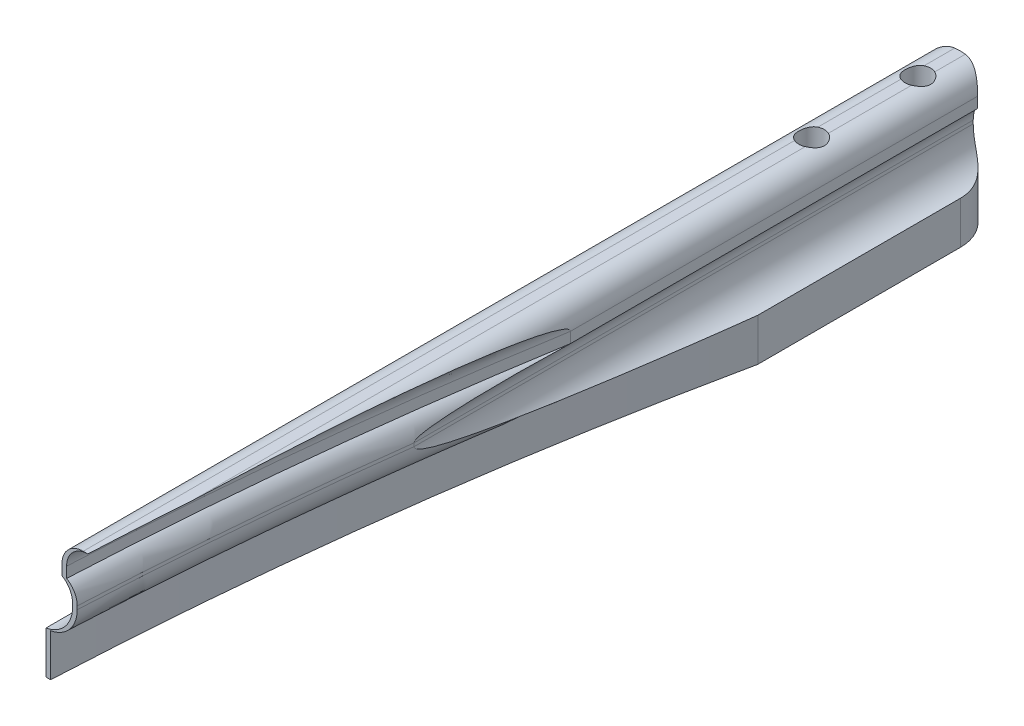
SolidWorks part; units mm, degrees
other "标注1"
sketch "草图3" plane through (-22.25, 4, -10) normal (-0.231, 0.6469, -0.7268) x (-0.9696, -0.2151, 0.1167)
other "标注2"
sketch "草图4" plane through (22.25, 8, -30) normal (0.0083, 0.0567, -0.9984) x (-0.9991, 0.0415, -0.0059)
ref_plane "前视基准面" through (0, 0, 0) normal (0, 0, 1) x (1, 0, 0)
ref_plane "上视基准面" through (0, 0, 0) normal (0, 1, 0) x (1, 0, 0)
ref_plane "右视基准面" through (0, 0, 0) normal (1, 0, 0) x (0, 0, -1)
other "Configuration Table"
sketch "草图1" plane through (0, 0, 0) normal (0, 1, 0) x (1, 0, 0)
  line L0 (-13.75, 12.5) -> (-13.75, -12.5)
  line L13 (-17.75, -12.5) -> (17.75, -12.5)
  line L21 (-17.75, -12.5) -> (-17.75, 12.5)
  line L22 (-17.75, 12.5) -> (17.75, 12.5)
  line L23 (17.75, -12.5) -> (17.75, 12.5)
  line L24 (-17.75, -12.5) -> (17.75, 12.5) construction
  line L25 (-17.75, 12.5) -> (17.75, -12.5) construction
  line L27 (13.75, 12.5) -> (13.75, -12.5)
  line L29 (-13.75, 0) -> (13.75, 0) construction
  line L32 (-22.25, 12.5) -> (22.25, 12.5)
  line L33 (-22.25, 12.5) -> (-22.25, 4.5)
  line L34 (-22.25, 4.5) -> (22.25, 4.5)
  line L35 (22.25, 12.5) -> (22.25, 4.5)
  point P0 (0, 0)
  point P15 (0, 4.5)
  dimension "D3" = 27.5
  dimension "D4" = 8
  dimension "D1" = 35.5
  dimension "D2" = 25
  dimension "D5" = 44.5
extrude "凸台-拉伸1" add sketch "草图1" along normal blind 4 contours L34 L21 L13 L0 | L34 L27 L13 L23 | L27 L34 L23 L22 | L21 L34 L0 L22 region at (-15.75, 0, -8.5) region at (-15.75, 0, 4) region at (15.75, 0, -8.5) region at (15.75, 0, 4)
extrude "凸台-拉伸2" add sketch "草图1<7>" along normal blind 3.5 contours L34 L35 L32 L33
sketch "草图1<7>" plane through (0, 0, 0) normal (0, 1, 0) x (1, 0, 0) same geometry as "草图1"
sketch "草图2" plane through (0, 0, -12.5) normal (0, 0, -1) x (-1, 0, 0)
  line L0 (18.25, 3.5) -> (22.25, 2)
  line L1 (22.25, 3.5) -> (18.25, 3.5)
  line L2 (22.25, 3.5) -> (22.25, 2)
  line L3 (22.25, 2) -> (18.25, 2) construction
  line L4 (18.25, 3.5) -> (18.25, 2) construction
  line L5 (-22.25, 2) -> (-18.25, 3.5)
  line L6 (-22.25, 3.5) -> (-18.25, 3.5)
  line L7 (-22.25, 3.5) -> (-22.25, 2)
  line L8 (-22.25, 2) -> (-18.25, 2) construction
  line L9 (-18.25, 3.5) -> (-18.25, 2) construction
  line L10 (13.75, 3.5) -> (-13.75, 3.5) construction
  line L11 (-13.25, 3.5) -> (-9.25, 3.5)
  line L12 (-13.25, 3.5) -> (-13.25, 2) construction
  line L13 (-13.25, 2) -> (-9.25, 2) construction
  line L14 (-9.25, 3.5) -> (-9.25, 2)
  line L15 (-13.75, 3.5) -> (-13.25, 3.5) construction
  line L16 (13.25, 3.5) -> (9.25, 3.5)
  line L17 (13.25, 3.5) -> (13.25, 2) construction
  line L18 (13.25, 2) -> (9.25, 2) construction
  line L19 (9.25, 3.5) -> (9.25, 2)
  line L20 (13.25, 3.5) -> (13.75, 3.5) construction
  line L21 (17.75, 3.5) -> (18.25, 3.5) construction
  line L22 (-13.25, 3.5) -> (-9.25, 2)
  line L23 (9.25, 2) -> (13.25, 3.5)
  line L24 (-9.25, 2) -> (9.25, 2)
  line L25 (-9.25, 3.5) -> (9.25, 3.5)
  line L26 (-15.75, 4) -> (-15.75, 6.5) construction
  line L27 (14.5, 8) -> (17, 8)
  line L28 (14.5, 8) -> (14.5, 6.5)
  line L29 (14.5, 6.5) -> (17, 6.5)
  line L30 (17, 8) -> (17, 6.5)
  line L31 (-17, 8) -> (-14.5, 8)
  line L32 (-17, 8) -> (-17, 6.5)
  line L33 (-17, 6.5) -> (-14.5, 6.5)
  line L34 (-14.5, 8) -> (-14.5, 6.5)
  line L35 (-13.75, 4) -> (-17.75, 4) construction
  line L36 (15.75, 6.5) -> (15.75, 4) construction
  line L37 (17.75, 4) -> (13.75, 4) construction
  line L38 (15, 6.5) -> (15, 4)
  line L39 (16.5, 6.5) -> (16.5, 4)
  line L40 (16.5, 4) -> (15.75, 4)
  line L41 (15.75, 4) -> (15, 4)
  line L42 (-16.5, 6.5) -> (-16.5, 4)
  line L43 (-16.5, 4) -> (-15.75, 4)
  line L44 (-15.75, 4) -> (-15, 4)
  line L45 (-15, 4) -> (-15, 6.5)
  line M9 (22.25, 3.5) -> (17.75, 3.5)
  line M11 (17.75, 4) -> (13.75, 4)
  line M13 (13.75, 3.5) -> (-13.75, 3.5)
  line M15 (-13.75, 4) -> (-17.75, 4)
  line M17 (-17.75, 3.5) -> (-22.25, 3.5)
  line M18 (-22.25, 3.5) -> (-22.25, 0)
  line M20 (22.25, 0) -> (22.25, 3.5)
  dimension "D1" = 4
  dimension "D2" = 1.5
  dimension "D3" = 2.5
  dimension "D4" = 1.5
  dimension "D5" = 2.5
  dimension "D6" = 1.5
extrude "切除-拉伸1" cut sketch "草图2" against normal through all contours L14 L24 L19 M13 | L19 L23 M13 | L22 L14 M13 | L5 M18 M17 | L0 M9 M20 region at (-20.9167, 3, -12.5) region at (20.9167, 3, -12.5) region at (10.5833, 3, -12.5) region at (0, 2.75, -12.5) region at (-10.5833, 3, -12.5)
extrude "凸台-拉伸4" add sketch "草图2<3>" against normal through all contours L34 L31 L32 L33 | L45 L33 L42 M15 | L30 L27 L28 L29 | L39 L29 L38 M11 region at (-15.75, 7.25, -12.5) region at (-15.75, 5.25, -12.5) region at (15.75, 7.25, -12.5) region at (15.75, 5.25, -12.5)
sketch "草图2<3>" plane through (0, 0, -12.5) normal (0, 0, -1) x (-1, 0, 0) same geometry as "草图2"
fillet "圆角1" radius 1 4 edges at (-16.5, 6.5, 0) (-15, 6.5, 0) (15, 6.5, 0) (16.5, 6.5, 0)
fillet "圆角2" radius 1.5 4 edges at (16.5, 4, 0) (15, 4, 0) (-15, 4, 0) (-16.5, 4, 0)
fillet "圆角3" radius 1 4 edges at (-17, 8, 0) (14.5, 8, 0) (17, 8, 0) (-14.5, 8, 0)
sketch "草图8" plane through (22.25, 0, 0) normal (1, 0, 0) x (0, 0, -1)
  line L0 (8.5, 0) -> (8.5, 18.5305)
  line L1 (12.5, 0) -> (4.5, 0) construction
mirror "镜向2" about plane through (0, 4, 12.5) normal (0, 0, -1) of bodies 192
sketch "草图10" plane through (0, 0, 0) normal (0, -1, 0) x (1, 0, 0)
  line L0 (-22.25, 29.5) -> (-17.75, 29.5) construction
  line L1 (-22.25, 37.5) -> (-17.75, 37.5)
  line L2 (-22.25, 37.5) -> (-22.25, 29.5)
  line L3 (-22.25, 29.5) -> (-17.75, 29.5)
  line L4 (-17.75, 37.5) -> (-17.75, 29.5)
  line L11 (-22.25, -4.5) -> (-17.75, -4.5) construction
  line L12 (-22.25, -12.5) -> (-17.75, -12.5)
  line L13 (-22.25, -12.5) -> (-22.25, -4.5)
  line L14 (-22.25, -4.5) -> (-17.75, -4.5)
  line L15 (-17.75, -12.5) -> (-17.75, -4.5)
  line L21 (-22.25, 37.5) -> (22.25, 37.5) construction
  line L22 (-13.75, 37.5) -> (22.25, 37.5)
  line L23 (-13.75, 37.5) -> (-13.75, -12.5)
  line L24 (-13.75, -12.5) -> (22.25, -12.5)
  line L25 (22.25, 37.5) -> (22.25, -12.5)
  line L26 (-22.25, -12.5) -> (22.25, -12.5) construction
  line L27 (-13.75, -4.5) -> (-13.75, 29.5) construction
extrude "切除-拉伸2" cut sketch "草图10" against normal through all
sketch "草图11" plane through (0, 0, 0) normal (0, -1, 0) x (-1, 0, 0)
  line L0 (17.75, -37.5) -> (17.75, 12.5) construction
  line L1 (13.75, 12.5) -> (13.75, -37.5) construction
  line L2 (17.75, 12.5) -> (13.75, 12.5) construction
  circle A0 centre (15.75, 10.5) radius 2
  line M2 (17.75, 12.5) -> (13.75, 12.5)
  line M3 (13.75, 12.5) -> (13.75, -37.5)
  line M5 (17.75, -37.5) -> (17.75, 12.5)
extrude "切除-拉伸3" cut sketch "草图11" against normal through all contours A0 M5 M2 | A0 M2 M3 region at (-17.3033, 0, -12.0533) region at (-14.1967, 0, -12.0533)
sketch "草图16" plane through (0, 0, 37.5) normal (0, 0, 1) x (1, 0, 0)
  line L8 (-17.75, 0) -> (-13.75, 0)
  line L9 (-13.75, 0) -> (-13.75, 4)
  line L10 (-15, 5.479) -> (-15, 5.634)
  line L11 (-14.5, 6.5) -> (-14.5, 7)
  line L12 (-15.5, 8) -> (-16, 8)
  line L13 (-17, 7) -> (-17, 6.5)
  line L14 (-16.5, 5.634) -> (-16.5, 5.479)
  line L15 (-17.75, 4) -> (-17.75, 0)
  line L16 (-17.75, 0) -> (-13.75, 0)
  line L17 (-13.75, 0) -> (-13.75, 4)
  line L18 (-15, 5.479) -> (-15, 5.634)
  line L19 (-14.5, 6.5) -> (-14.5, 7)
  line L20 (-15.5, 8) -> (-16, 8)
  line L21 (-17, 7) -> (-17, 6.5)
  line L22 (-16.5, 5.634) -> (-16.5, 5.479)
  line L23 (-17.75, 4) -> (-17.75, 0)
  arc A6 (-15, 5.479) -> (-13.75, 4) centre (-13.5, 5.479) ccw
  arc A7 (-14.5, 6.5) -> (-15, 5.634) centre (-14, 5.634) ccw
  arc A8 (-14.5, 7) -> (-15.5, 8) centre (-15.5, 7) ccw
  arc A9 (-16, 8) -> (-17, 7) centre (-16, 7) ccw
  arc A10 (-16.5, 5.634) -> (-17, 6.5) centre (-17.5, 5.634) ccw
  arc A11 (-17.75, 4) -> (-16.5, 5.479) centre (-18, 5.479) ccw
  arc A12 (-15, 5.479) -> (-13.75, 4) centre (-13.5, 5.479) ccw
  arc A13 (-14.5, 6.5) -> (-15, 5.634) centre (-14, 5.634) ccw
  arc A14 (-14.5, 7) -> (-15.5, 8) centre (-15.5, 7) ccw
  arc A15 (-16, 8) -> (-17, 7) centre (-16, 7) ccw
  arc A16 (-16.5, 5.634) -> (-17, 6.5) centre (-17.5, 5.634) ccw
  arc A17 (-17.75, 4) -> (-16.5, 5.479) centre (-18, 5.479) ccw
  dimension "D1" = 0
sketch "草图12" plane through (0, 0, 0) normal (0, -1, 0) x (1, 0, 0)
  line L0 (-17.75, 37.5) -> (-13.75, 37.5) construction
  line L1 (-17.75, 37.5) -> (-13.75, 37.5)
  line L2 (-17.75, 37.5) -> (-17.75, -12.5)
  line L3 (-17.75, -12.5) -> (-13.75, -12.5)
  line L4 (-13.75, 37.5) -> (-13.75, -12.5)
  line L5 (-17.75, 37.5) -> (-17.75, -10.5) construction
  arc A0 (-17.75, -10.5) -> (-13.75, -10.5) centre (-15.75, -10.5) ccw construction
extrude "切除-拉伸4" cut sketch "草图12" against normal blind 2
sketch "草图13" plane through (0, 8, 0) normal (0, 1, 0) x (1, 0, 0)
  line L0 (-16, 12.4843) -> (-16, -37.5) construction
  line L1 (-15.5, -37.5) -> (-15.5, 12.4843) construction
  line L2 (-15.75, 10.5) -> (-15.75, -22.774) construction
  circle A0 centre (-15.75, -22.774) radius 0.25
  circle A2 centre (-15.75, 10.5) radius 0.6
  arc A3 (-16, 12.4843) -> (-17, 12.0612) centre (-15.75, 10.5) ccw construction
  line M4 (-15.5, -37.5) -> (-15.5, 12.4843)
  line M7 (-16, -37.5) -> (-15.5, -37.5)
  dimension "D2" = 1.2
  dimension "D3" = 33.274
extrude "切除-拉伸5" cut sketch "草图13" against normal through all contours M4 M7 | A2 region at (-15.3558, 8, -10.5)
sketch "草图23" plane through (0, 0, 37.5) normal (0, 0, 1) x (1, 0, 0)
  line L0 (169.25, 37.7294) -> (169.25, -27.6564)
  line L16 (-17.75, 0) -> (-13.75, 0)
  line L17 (-13.75, 0) -> (-13.75, 4)
  line L18 (-15, 5.479) -> (-15, 5.634)
  line L19 (-14.5, 6.5) -> (-14.5, 7)
  line L20 (-15.5, 8) -> (-16, 8)
  line L21 (-17, 7) -> (-17, 6.5)
  line L22 (-16.5, 5.634) -> (-16.5, 5.479)
  line L23 (-17.75, 4) -> (-17.75, 0)
  arc A12 (-15, 5.479) -> (-13.75, 4) centre (-13.5, 5.479) ccw
  arc A13 (-14.5, 6.5) -> (-15, 5.634) centre (-14, 5.634) ccw
  arc A14 (-14.5, 7) -> (-15.5, 8) centre (-15.5, 7) ccw
  arc A15 (-16, 8) -> (-17, 7) centre (-16, 7) ccw
  arc A16 (-16.5, 5.634) -> (-17, 6.5) centre (-17.5, 5.634) ccw
  arc A17 (-17.75, 4) -> (-16.5, 5.479) centre (-18, 5.479) ccw
  dimension "D1" = 183
sketch "草图20" plane through (0, 2, 0) normal (0, -1, 0) x (1, 0, 0)
  line L0 (-15.75, -10.5) -> (-15.75, 22.7741)
  line L1 (-15.75, 13.2047) -> (-43.0541, 13.2047)
  line L2 (-17.75, 13.2047) -> (-15.75, 22.7741)
  line L3 (-17.75, 37.5) -> (-17.75, -10.5) construction
  line L4 (-15.75, 22.7741) -> (-8.4299, 22.7741)
  line L5 (-8.4299, 22.7741) -> (-8.4299, 31.2177)
  line L6 (-8.4299, 31.2177) -> (-21.8605, 31.2177)
  line L7 (-21.8605, 31.2177) -> (-21.8605, 13.2047)
  circle A2 centre (-15.75, -10.5) radius 0.6 construction
  dimension "D1" = 33.2741
  dimension "D2" = 23.7047
sketch "草图21" plane through (0, 8, 0) normal (0, 1, 0) x (1, 0, 0)
  line L0 (-15.75, 10.5) -> (-15.75, -51.8951)
  arc A0 (-15.5, 9.9546) -> (-15.5, 11.0454) centre (-15.75, 10.5) ccw construction
revolve "切除-旋转1" cut sketch "草图16" angle 360 about L0
sketch "草图24" plane through (0, 2, 0) normal (0, -1, 0) x (-1, 0, 0)
  circle A0 centre (15.75, 5.5) radius 0.6
  dimension "D2" = 1.2
  dimension "D1" = 5
extrude "切除-拉伸6" cut sketch "草图24" against normal through all
sketch "草图25" plane through (0, 8, 0) normal (0, 1, 0) x (1, 0, 0)
  line L0 (-17.75, -37.5) -> (-16.5, -37.5) construction
  line L1 (-18.1291, -34.2) -> (-8.5407, -34.2)
  line L2 (-18.1291, -34.2) -> (-18.1291, -37.5)
  line L3 (-18.1291, -37.5) -> (-8.5407, -37.5)
  line L4 (-8.5407, -34.2) -> (-8.5407, -37.5)
  dimension "D1" = 3.3
extrude "切除-拉伸7" cut sketch "草图25" against normal through all
sketch "草图26" plane through (0, 8, 0) normal (0, 1, 0) x (1, 0, 0)
  line L1 (-19.9573, -28.5) -> (-12.1103, -28.5)
  line L2 (-19.9573, -28.5) -> (-19.9573, -36.1764)
  line L3 (-19.9573, -36.1764) -> (-12.1103, -36.1764)
  line L4 (-12.1103, -28.5) -> (-12.1103, -36.1764)
  dimension "D1" = 39
extrude "切除-拉伸8" cut sketch "草图26" against normal through all
